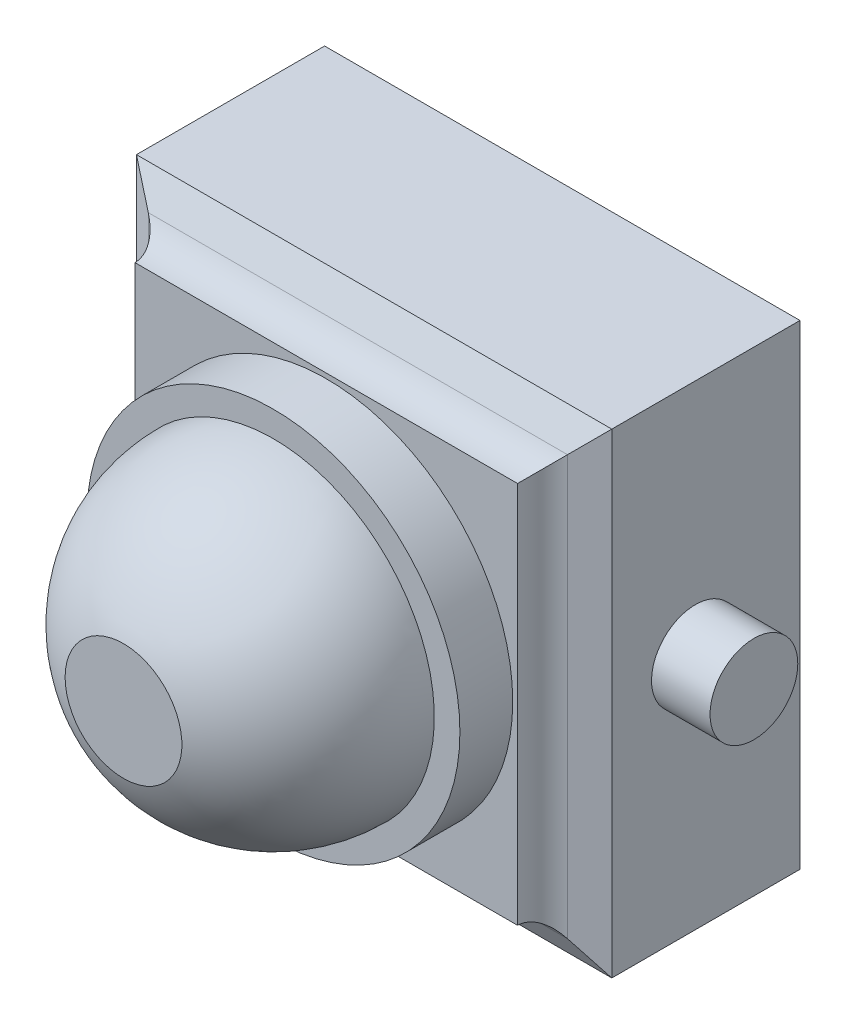
SolidWorks part; units mm, degrees
note: '?' marks a value the reader was unsure of.
ref_plane "Piano frontale" through (0, 0, 0) normal (0, 0, 1) x (1, 0, 0)
ref_plane "Piano superiore" through (0, 0, 0) normal (0, 1, 0) x (1, 0, 0)
ref_plane "Piano destro" through (0, 0, 0) normal (1, 0, 0) x (0, 0, -1)
other "Centro di massa"
sketch "Schizzo1" plane through (0, 0, 0) normal (0, 0, 1) x (1, 0, 0)
  line L1 (-32.5, 32.5) -> (32.5, 32.5)
  line L2 (-32.5, 32.5) -> (-32.5, -32.5)
  line L3 (-32.5, -32.5) -> (32.5, -32.5)
  line L4 (32.5, 32.5) -> (32.5, -32.5)
  line L5 (-32.5, 32.5) -> (32.5, -32.5) construction
  line L6 (-32.5, -32.5) -> (32.5, 32.5) construction
  point P0 (0, 0)
  dimension "D1" = 65
  dimension "D2" = 65
extrude "Estrusione-Estrusione1" add sketch "Schizzo1" along normal blind 39.5
ref_axis "Assi1" through (0, 0, -3) along (0, 0, 1)?
sketch "Schizzo2" plane through (0, 0, 0) normal (0, 0, -1) x (-1, 0, 0)
  line L0 (0, -32.5) -> (0, 32.5) construction
  line L1 (32.5, -32.5) -> (-32.5, -32.5) construction
  line L2 (-32.5, 32.5) -> (32.5, 32.5) construction
  line L3 (32.5, 0) -> (-32.5, 0) construction
  line L4 (32.5, 32.5) -> (32.5, -32.5) construction
  line L5 (-32.5, -32.5) -> (-32.5, 32.5) construction
  circle A0 centre (24, -18) radius 1.5
  circle A1 centre (-24, -18) radius 1.5
  circle A2 centre (-24, 18) radius 1.5
  circle A3 centre (24, 18) radius 1.5
  dimension "D3" = 3
  dimension "D1" = 36
  dimension "D2" = 48
extrude "Taglio-Estrusione1" cut sketch "Schizzo2" against normal blind 5
sketch "Schizzo3" plane through (32.5, 0, 0) normal (1, 0, 0) x (0, 0, -1)
  line L0 (0, 0) -> (-39.5, 0) construction
  line L1 (-39.5, -32.5) -> (-39.5, 32.5) construction
  circle A0 centre (-14.3, 0) radius 6
  point P5 (-14.3, 0)
  dimension "D2" = 12
  dimension "D1" = 14.3
extrude "Estrusione-Estrusione2" add sketch "Schizzo3" along normal blind 8
sketch "Schizzo5" plane through (0, 0, 0) normal (-1, 0, 0) x (0, 0, 1)
  line L0 (39.5, -32.5) -> (39.5, -26.16)
  line L1 (39.5, 32.5) -> (39.5, -32.5) construction
  line L2 (39.5, -26.16) -> (32.2768, -26.1602)
  line L3 (27.9467, -28.6603) -> (25.73, -32.5)
  line L4 (39.5, -32.5) -> (0, -32.5) construction
  line L5 (25.73, -32.5) -> (39.5, -32.5)
  arc A0 (32.2768, -26.1602) -> (27.9467, -28.6603) centre (32.2769, -31.1602) ccw
  point P11 (29.39, -26.1603)
  dimension "D5" = 5
  dimension "D1" = 13.77
  dimension "D2" = 6.34
  dimension "D3" = 120
  dimension "D4" = 10.11
extrude "Taglio-Estrusione2" cut sketch "Schizzo5" along direction (1, 0, 0) on the side against the normal up to next (32.5 mm away) and the other way up to next (32.5 mm away) contours L0 L2 A0 L3 L5
mirror "Specchia1" about plane through (0, 0, 0) normal (0, 1, 0) of "Taglio-Estrusione2"
pattern_circular "RipetizioneCircolare1" count 2 every 90 about axis through (0, 0, -3) along (0, 0, 1) of "Taglio-Estrusione2"
sketch "Schizzo4" plane through (0, 0, 39.5) normal (0, 0, 1) x (1, 0, 0)
  line L0 (-26.1602, -26.1602) -> (-28.6603, -28.6603) construction
  line L8 (-26.1602, -26.1602) -> (26.1602, -26.1602)
  line L9 (26.1602, -26.1602) -> (26.1602, 26.1602)
  line L10 (26.1602, 26.1602) -> (-26.1602, 26.1602)
  line L11 (-26.1602, 26.1602) -> (-26.1602, -26.1602)
  circle A0 centre (0, 0) radius 25.5
  dimension "D1" = 51
  dimension "D2" = 52.3204
extrude "Taglio-Estrusione3" cut sketch "Schizzo4" against normal up to vertex (7.2232 mm away)
sketch "Schizzo7" plane through (0, 0, 39.5) normal (0, 0, 1) x (1, 0, 0)
  line L0 (0, -22) -> (0, 22)
  line L1 (0, 0) -> (0, 25.5) construction
  arc A0 (0, 22) -> (0, -22) centre (0, 0) cw
  circle A1 centre (0, 0) radius 25.5 construction
  point P4 (0, 0)
  dimension "D1" = 44
revolve "Rivoluzione2" add sketch "Schizzo7" angle 180 about L1
sketch "Schizzo8" plane through (0, 0, 0) normal (0, 1, 0) x (1, 0, 0)
  line L0 (-32.5, 0) -> (32.5, 0) construction
  line L1 (-10, -62) -> (10, -62)
  line L2 (-10, -62) -> (-10, -60)
  line L3 (-10, -60) -> (10, -60)
  line L4 (10, -62) -> (10, -60)
  line L5 (-10, -62) -> (10, -60) construction
  line L6 (-10, -60) -> (10, -62) construction
  point P0 (0, -61)
  point P10 (10, -61)
  dimension "D1" = 60
  dimension "D2" = 20
  dimension "D3" = 2
extrude "Taglio-Estrusione4" cut sketch "Schizzo8" against normal through all both and the other way through all
other "Punto di riferimento centro di massa1"
